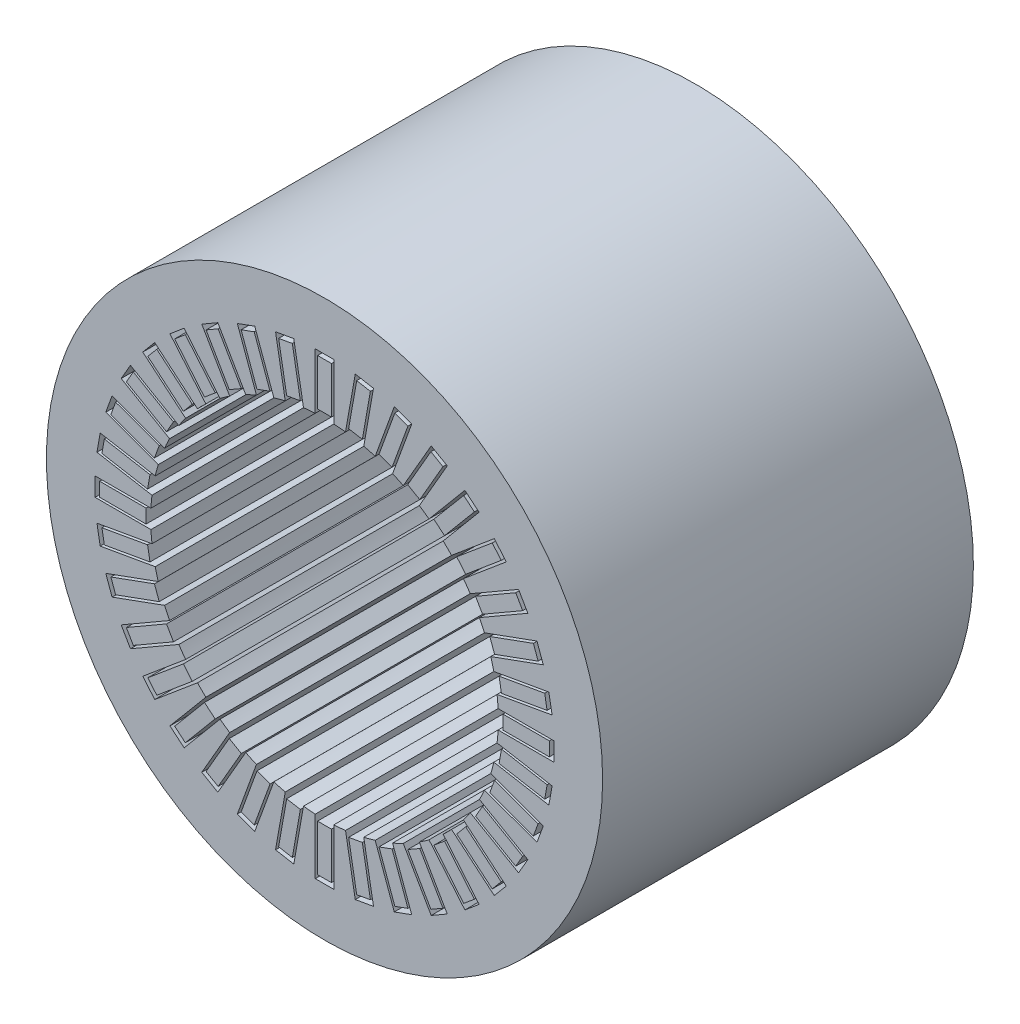
SolidWorks part; units mm, degrees
ref_plane "Front Plane" through (0, 0, 0) normal (0, 0, 1) x (1, 0, 0)
ref_plane "Top Plane" through (0, 0, 0) normal (0, 1, 0) x (1, 0, 0)
ref_plane "Right Plane" through (0, 0, 0) normal (1, 0, 0) x (0, 0, -1)
sketch "Sketch1" plane through (0, 0, 0) normal (0, 0, 1) x (1, 0, 0)
  circle A0 centre (0, 0) radius 60
  circle A1 centre (0, 0) radius 37.5
extrude "Nucleo" add sketch "Sketch1" along normal blind 80
ref_axis "Eje_Z" through (0, 0, -4) along (0, 0, 1)
sketch "Sketch5" plane through (0, 0, 0) normal (0, 0, 1) x (1, 0, 0)
  line L1 (37, -2) -> (49.5, -2)
  line L2 (37, -2) -> (37, 2)
  line L3 (37, 2) -> (49.5, 2)
  line L4 (49.5, -2) -> (49.5, 2)
extrude "Ranura" cut sketch "Sketch5" along normal through all
pattern_circular "Ranuras_x36" count 36 over 360 about axis through (0, 0, -4) along (0, 0, 1) of "Ranura"
sketch "Sketch6" plane through (0, 0, 0) normal (0, 0, 1) x (1, 0, 0)
  line L1 (38.5, -1.5) -> (48.5, -1.5)
  line L2 (38.5, -1.5) -> (38.5, 1.5)
  line L3 (38.5, 1.5) -> (48.5, 1.5)
  line L4 (48.5, -1.5) -> (48.5, 1.5)
extrude "Bobina" add sketch "Sketch6" along normal blind 80 separate body
pattern_circular "Bobinas_x36" count 36 over 360 about axis through (0, 0, -4) along (0, 0, 1) of bodies 104
